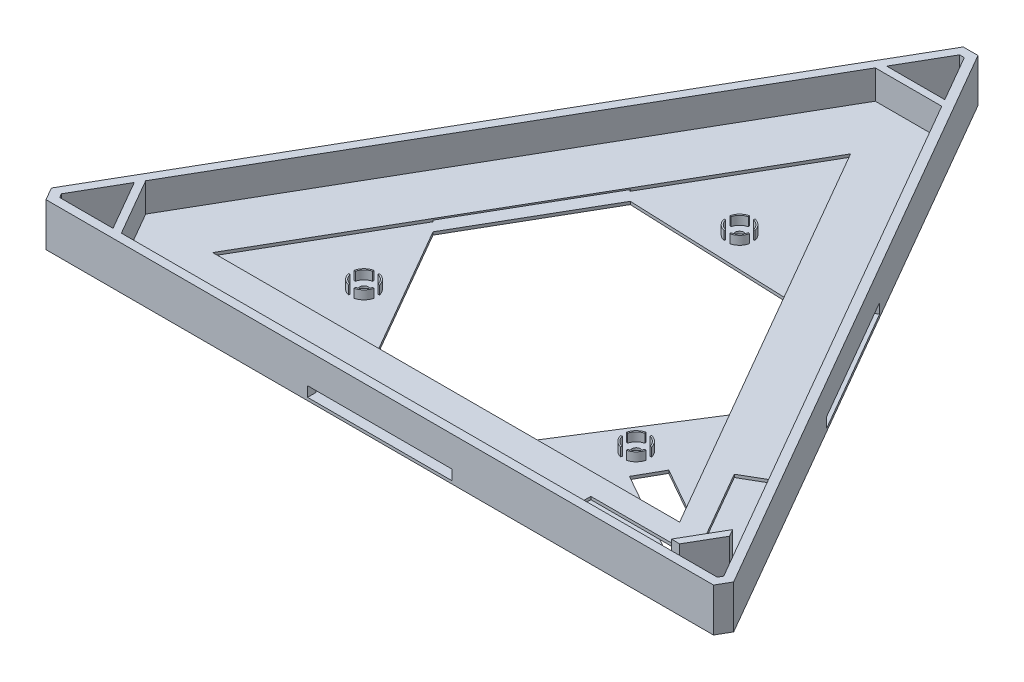
SolidWorks part; units mm, degrees
ref_plane "Front Plane" through (0, 0, 0) normal (0, 0, 1) x (1, 0, 0)
ref_plane "Top Plane" through (0, 0, 0) normal (0, 1, 0) x (1, 0, 0)
ref_plane "Right Plane" through (0, 0, 0) normal (1, 0, 0) x (0, 0, -1)
sketch "Sketch1" plane through (0, 0, 0) normal (0, 1, 0) x (1, 0, 0)
  line L0 (351.2729, 67.6655) -> (468.273, -134.9846)
  line L1 (347.2728, 67.6655) -> (347.2728, 65.1655) construction
  line L2 (409.773, -33.6595) -> (407.6079, -34.9095) construction
  line L3 (468.273, -134.9846) -> (464.2732, -141.9124)
  line L4 (230.2733, -141.9124) -> (464.2732, -141.9124)
  line L5 (230.2733, -141.9124) -> (226.2727, -134.9842)
  line L6 (226.2727, -134.9842) -> (343.2728, 67.6655)
  line L7 (353.4142, 63.9567) -> (351.2491, 62.7067) construction
  line L8 (347.2733, -141.9124) -> (347.2733, -139.4124) construction
  line L9 (231.7167, -139.4124) -> (462.8299, -139.4124)
  line L10 (284.7727, -33.6594) -> (286.9378, -34.9094) construction
  line L11 (344.7161, 65.1655) -> (349.8295, 65.1655)
  line L12 (465.3862, -134.9846) -> (349.8295, 65.1655)
  line L13 (466.2731, -138.4485) -> (464.1081, -137.1985) construction
  line L14 (462.8299, -139.4124) -> (465.3862, -134.9846)
  line L15 (229.1594, -134.9842) -> (344.7161, 65.1655)
  line L16 (229.1594, -134.9842) -> (231.7167, -139.4124)
  line L17 (286.9378, -34.9094) -> (287.3708, -35.1594) construction
  line L18 (230.438, -137.1983) -> (230.871, -136.9483) construction
  line L19 (232.0053, -138.9123) -> (229.7368, -134.9842)
  line L20 (343.2728, 67.6655) -> (351.2729, 67.6655)
  line L21 (345.0048, 64.6655) -> (229.7368, -134.9842)
  line L22 (349.5409, 64.6655) -> (345.0048, 64.6655)
  line L23 (249.0568, -126.4468) -> (246.8918, -127.697) construction
  line L24 (407.6079, -34.9095) -> (407.1749, -35.1595) construction
  line L26 (233.4463, -136.4089) -> (251.9226, -136.4093)
  line L27 (464.8089, -134.9846) -> (462.5412, -138.9123)
  line L28 (462.5412, -138.9123) -> (232.0053, -138.9123)
  line L29 (251.9226, -136.4093) -> (241.8609, -118.9847)
  line L30 (241.8609, -118.9847) -> (232.6236, -134.9842)
  line L31 (232.6236, -134.9842) -> (233.4463, -136.4089)
  line L33 (287.3708, -35.1594) -> (289.5359, -36.4094) construction
  line L34 (254.8093, -136.4089) -> (243.3042, -116.4848)
  line L35 (335.7675, 43.666) -> (243.3042, -116.4848)
  line L36 (358.7782, 43.666) -> (335.7675, 43.666)
  line L38 (289.5359, -36.4094) -> (306.8564, -46.4094) construction
  line L41 (461.939, -134.9846) -> (461.1164, -136.4093)
  line L42 (347.2688, -136.4172) -> (347.2688, -116.4172) construction
  line L43 (442.6021, -136.4093) -> (452.6999, -118.9847)
  line L44 (245.2636, -119.878) -> (249.0568, -126.4468) construction
  line L45 (452.6999, -118.9847) -> (461.939, -134.9846)
  line L48 (461.1164, -136.4093) -> (442.6021, -136.4093)
  line L49 (405.0134, -36.4027) -> (387.6936, -46.404) construction
  line L50 (306.8564, -46.4094) -> (466.2731, -138.4485) construction
  line L51 (357.3348, 46.166) -> (337.2109, 46.166)
  line L52 (337.2109, 46.166) -> (346.4484, 62.1659)
  line L53 (346.4484, 62.1659) -> (348.0966, 62.164)
  line L54 (348.0966, 62.164) -> (357.3348, 46.166)
  line L55 (228.273, -138.4483) -> (387.6936, -46.404) construction
  line L56 (347.2688, -116.4172) -> (347.2728, 43.666) construction
  line L57 (266.4391, -116.428) -> (428.1137, -116.4172)
  line L58 (347.2736, 23.6092) -> (428.1137, -116.4172)
  line L59 (266.4391, -116.428) -> (347.2736, 23.6092)
  line L60 (439.7283, -136.4254) -> (439.7283, -132.9254) construction
  line L61 (451.2487, -116.4715) -> (448.6507, -117.9717) construction
  line L62 (452.6999, -118.9847) -> (358.7782, 43.666)
  line L63 (442.6021, -136.4093) -> (254.8093, -136.4089)
  line L64 (441.749, -132.9254) -> (444.621, -132.9254)
  line L65 (448.6507, -117.9717) -> (450.9647, -121.979) construction
  line L66 (449.5167, -119.4714) -> (450.9647, -121.979)
  line L67 (441.749, -132.9254) -> (449.5167, -119.4714)
  line L68 (450.9647, -121.979) -> (444.621, -132.9254)
  line L69 (461.939, -134.9846) -> (427.2809, -114.9747) construction
  line L70 (461.1164, -136.4093) -> (426.4891, -116.4173) construction
  line L73 (405.0134, -134.9846) -> (439.7283, -134.9846)
  line L74 (405.0134, -134.9846) -> (405.0134, -124.0609)
  line L75 (405.0134, -124.0609) -> (439.7283, -124.0609)
  line L76 (439.7283, -134.9846) -> (439.7283, -124.0609)
  line L77 (405.0134, -124.0609) -> (430.3202, -80.2282) construction
  line L78 (405.0134, -134.9846) -> (433.4739, -85.6896) construction
  line L79 (461.1164, -136.4093) -> (424.3464, -72.7321) construction
  line L80 (432.6513, -87.1143) -> (423.1904, -92.5775)
  line L81 (432.6513, -87.1143) -> (450.1194, -117.365)
  line L82 (423.1904, -92.5775) -> (440.6585, -122.8281)
  line L83 (450.1194, -117.365) -> (440.6585, -122.8281)
  point P13 (407.6079, -34.9095)
  point P20 (464.1081, -137.1985)
  point P23 (347.2733, -139.4124)
  point P25 (347.2732, -141.9124)
  point P27 (347.2728, 65.1655)
  point P31 (286.9378, -34.9094)
  point P37 (287.3708, -35.1594)
  point P39 (230.871, -136.9483)
  point P41 (347.2728, 64.6655)
  point P45 (407.1749, -35.1595)
  point P50 (246.8918, -127.697)
  point P56 (289.5359, -36.4094)
  point P58 (249.0568, -126.4468)
  point P60 (347.2728, 43.666)
  point P62 (345.0048, -136.4089)
  point P64 (445.4885, -126.4485)
  point P71 (447.651, -127.697)
  point P77 (347.2728, 46.166)
  point P84 (347.2688, -116.4172)
  point P87 (387.6936, -46.404)
  point P89 (306.8564, -46.4094)
  point P100 (405.0134, -36.4027)
  dimension "D1" = 2.5
  dimension "D2" = 2.5
  dimension "D3" = 2.5
  dimension "D4" = 2.5
  dimension "D5" = 2.5
  dimension "D6" = 2.5
  dimension "D7" = 0.5
  dimension "D8" = 0.5
  dimension "D9" = 0.5
  dimension "D10" = 2.5
  dimension "D11" = 2.5
  dimension "D12" = 20
  dimension "D13" = 20
  dimension "D14" = 20
  dimension "D15" = 3.5
  dimension "D16" = 3
extrude "Boss-Extrude1" add sketch "Sketch1" along normal blind 1 contours L36 L35 L34 L57 L59 L58 region at (251.4484, 0, 125.0658)
extrude "Boss-Extrude2" add sketch "Sketch1<9>" along normal blind 11 contours L28 L27 L22 L21 L19 L31 L30 L29 L26 L34 L35 L36 L41 L48 L43 L45 L53 L54 L51 L52 | L68 L64 L67 L66 region at (230.7087, 0, 137.042)
sketch "Sketch1<9>" plane through (0, 0, 0) normal (0, 1, 0) x (1, 0, 0) same geometry as "Sketch1"
extrude "Boss-Extrude3" add sketch "Sketch1<10>" along normal blind 5 and the other way blind 3 contours L28 L27 L22 L21 L19 L31 L30 L29 L26 L34 L35 L36 L41 L48 L43 L45 L53 L54 L51 L52 | L68 L64 L67 L66 region at (230.7087, 0, 137.042)
sketch "Sketch1<10>" plane through (0, 0, 0) normal (0, 1, 0) x (1, 0, 0) same geometry as "Sketch1"
sketch "Sketch3" plane through (290.5896, 0, -167.772) normal (0.866, 0, -0.5) x (-0.5, 0, -0.866)
  line L1 (-261.593, -6.5) -> (-211.593, -6.5)
  line L2 (-261.593, -6.5) -> (-261.593, 0.5)
  line L3 (-261.593, 0.5) -> (-211.593, 0.5)
  line L4 (-211.593, -6.5) -> (-211.593, 0.5)
  line L5 (-261.593, -6.5) -> (-211.593, 0.5) construction
  line L6 (-261.593, 0.5) -> (-211.593, -6.5) construction
  point P0 (-236.593, -3)
  dimension "D1" = 50
  dimension "D2" = 7
extrude "Cut-Extrude3" cut sketch "Sketch3" against normal blind 25
sketch "Sketch5" plane through (0, 0, 139.4124) normal (0, 0, 1) x (1, 0, 0)
  line L0 (231.7167, -3) -> (462.8299, -3) construction
  line L1 (322.2733, -6.5) -> (372.2733, -6.5)
  line L2 (322.2733, -6.5) -> (322.2733, 0.5)
  line L3 (322.2733, 0.5) -> (372.2733, 0.5)
  line L4 (372.2733, -6.5) -> (372.2733, 0.5)
  line L5 (322.2733, -6.5) -> (372.2733, 0.5) construction
  line L6 (322.2733, 0.5) -> (372.2733, -6.5) construction
  point P0 (347.2733, -3)
  dimension "D1" = 50
  dimension "D2" = 7
extrude "Cut-Extrude4" cut sketch "Sketch5" against normal blind 25
sketch "Sketch6" plane through (230.3194, 0, 132.9752) normal (-0.866, 0, -0.5) x (-0.5, 0, 0.866)
  line L0 (2.3199, -3) -> (-228.7932, -3) construction
  line L1 (-138.2367, -6.5) -> (-88.2367, -6.5)
  line L2 (-138.2367, -6.5) -> (-138.2367, 0.5)
  line L3 (-138.2367, 0.5) -> (-88.2367, 0.5)
  line L4 (-88.2367, -6.5) -> (-88.2367, 0.5)
  line L5 (-138.2367, -6.5) -> (-88.2367, 0.5) construction
  line L6 (-138.2367, 0.5) -> (-88.2367, -6.5) construction
  point P0 (-113.2367, -3)
  dimension "D1" = 50
  dimension "D2" = 7
extrude "Cut-Extrude5" cut sketch "Sketch6" against normal blind 25
sketch "Sketch8" plane through (0, -3, 0) normal (0, -1, 0) x (1, 0, 0)
  line L1 (349.8295, -65.1655) -> (465.3862, 134.9846)
  line L2 (465.3862, 134.9846) -> (462.8299, 139.4124)
  line L6 (462.8299, 139.4124) -> (231.7167, 139.4124)
  line L7 (450.147, 123.2807) -> (452.6999, 118.9847)
  line L9 (452.6999, 118.9847) -> (461.939, 134.9846)
  line L12 (461.939, 134.9846) -> (461.1164, 136.4093)
  line L17 (461.1164, 136.4093) -> (442.6021, 136.4093)
  line L19 (322.2733, 116.4243) -> (294.3582, 68.0611)
  line L20 (294.3582, 68.0611) -> (319.3545, 24.7577)
  line L21 (319.3545, 24.7577) -> (376.4737, 26.9694)
  line L22 (376.4737, 26.9694) -> (401.4727, 70.2712)
  line L23 (401.4727, 70.2712) -> (372.2733, 116.4209)
  line L24 (372.2733, 116.4209) -> (322.2733, 116.4243)
  line L25 (386.873, 93.3461) -> (395.3235, 98.6928) construction
  line L30 (308.3157, 92.2427) -> (299.6549, 97.2417) construction
  line L31 (347.9141, 25.8635) -> (348.3013, 15.8635) construction
  line L34 (401.698, 107.3846) -> (445.2267, 131.9864)
  line L35 (450.147, 123.2807) -> (406.6183, 98.6788)
  line L36 (401.698, 107.3846) -> (406.6183, 98.6788)
  line L37 (231.7167, 139.4124) -> (229.1594, 134.9842)
  line L39 (233.4463, 136.4089) -> (251.9226, 136.4093)
  line L40 (251.9226, 136.4093) -> (241.8609, 118.9847)
  line L41 (241.8609, 118.9847) -> (232.6236, 134.9842)
  line L42 (232.6236, 134.9842) -> (233.4463, 136.4089)
  line L43 (349.8295, -65.1655) -> (344.7161, -65.1655)
  line L44 (344.7161, -65.1655) -> (229.1594, 134.9842)
  line L45 (337.2109, -46.166) -> (357.3348, -46.166)
  line L46 (357.3348, -46.166) -> (348.0966, -62.164)
  line L47 (348.0966, -62.164) -> (346.4484, -62.1659)
  line L48 (346.4484, -62.1659) -> (337.2109, -46.166)
  line L49 (442.6021, 136.4093) -> (445.2267, 131.9864)
  circle A0 centre (395.3235, 98.6928) radius 1.5
  circle A1 centre (348.3013, 15.8635) radius 1.5
  circle A2 centre (299.6549, 97.2417) radius 1.5
  dimension "D6" = 3
  dimension "D7" = 3
  dimension "D8" = 3
  dimension "D1" = 10
  dimension "D2" = 50
  dimension "D3" = 10
  dimension "D4" = 10
  dimension "D5" = 10
extrude "Boss-Extrude5" add sketch "Sketch8" along normal blind 1
sketch "Sketch12" plane through (0, -3, 0) normal (0, 1, 0) x (1, 0, 0)
  line L0 (348.3013, -11.8635) -> (348.3013, -11.3635) construction
  line L1 (348.3013, -11.3635) -> (349.2951, -11.4746) construction
  line L2 (349.2951, -11.4746) -> (349.1847, -11.9623)
  line L3 (348.3013, -11.3635) -> (347.3075, -11.4746) construction
  line L4 (347.3075, -11.4746) -> (347.4179, -11.9623)
  line L5 (352.3013, -15.8635) -> (352.8013, -15.8635) construction
  line L6 (344.3013, -15.8635) -> (343.8013, -15.8635) construction
  line L7 (348.3013, -19.8635) -> (348.3013, -20.3635) construction
  line L8 (352.8013, -15.8635) -> (352.6902, -14.8697) construction
  line L9 (352.8013, -15.8635) -> (352.6902, -16.8573) construction
  line L10 (343.8013, -15.8635) -> (343.9124, -14.8697) construction
  line L11 (343.8013, -15.8635) -> (343.9124, -16.8573) construction
  line L12 (348.3013, -20.3635) -> (349.2951, -20.2524) construction
  line L13 (348.3013, -20.3635) -> (347.3075, -20.2524) construction
  line L14 (343.9124, -14.8697) -> (348.3013, -15.8635) construction
  line L15 (348.3013, -15.8635) -> (352.6902, -14.8697) construction
  line L16 (343.9124, -16.8573) -> (348.3013, -15.8635) construction
  line L17 (348.3013, -15.8635) -> (352.6902, -16.8573) construction
  line L18 (347.3075, -20.2524) -> (348.3013, -15.8635) construction
  line L19 (348.3013, -15.8635) -> (349.2951, -20.2524) construction
  line L20 (343.9124, -14.8697) -> (344.4001, -14.9801)
  line L21 (343.9124, -16.8573) -> (344.4001, -16.7469)
  line L22 (347.3075, -20.2524) -> (347.4179, -19.7648)
  line L23 (349.2951, -20.2524) -> (349.1847, -19.7648)
  line L24 (352.6902, -14.8697) -> (352.2025, -14.9801)
  line L25 (352.6902, -16.8573) -> (352.2025, -16.7469)
  line L26 (395.3235, -94.1928) -> (395.3235, -98.6928) construction
  line L27 (395.3235, -98.6928) -> (390.8235, -98.6928) construction
  line L28 (390.8235, -98.6928) -> (390.9347, -97.699) construction
  line L29 (399.8235, -98.6928) -> (395.3235, -98.6928) construction
  line L30 (395.3235, -98.6928) -> (395.3235, -103.1928) construction
  line L31 (395.3235, -103.1928) -> (396.3173, -103.0817) construction
  line L32 (395.3235, -94.1928) -> (396.3173, -94.3039) construction
  line L33 (395.3235, -94.1928) -> (394.3297, -94.3039) construction
  line L34 (399.7124, -97.699) -> (399.8235, -98.6928) construction
  line L35 (399.8235, -98.6928) -> (399.7124, -99.6866) construction
  line L36 (390.9347, -99.6866) -> (390.8235, -98.6928) construction
  line L37 (394.3297, -103.0817) -> (395.3235, -103.1928) construction
  line L38 (394.3297, -94.3039) -> (395.3235, -98.6928) construction
  line L39 (395.3235, -98.6928) -> (396.3173, -94.3039) construction
  line L40 (390.9347, -99.6866) -> (395.3235, -98.6928) construction
  line L41 (395.3235, -98.6928) -> (390.9347, -97.699) construction
  line L42 (399.7124, -97.699) -> (395.3235, -98.6928) construction
  line L43 (395.3235, -98.6928) -> (399.7124, -99.6866) construction
  line L44 (394.3297, -103.0817) -> (395.3235, -98.6928) construction
  line L45 (395.3235, -98.6928) -> (396.3173, -103.0817) construction
  line L46 (394.3297, -94.3039) -> (394.4402, -94.7916)
  line L47 (396.3173, -94.3039) -> (396.2069, -94.7916)
  line L48 (399.7124, -97.699) -> (399.2248, -97.8094)
  line L49 (399.7124, -99.6866) -> (399.2248, -99.5762)
  line L50 (396.3173, -103.0817) -> (396.2069, -102.5941)
  line L51 (394.3297, -103.0817) -> (394.4402, -102.5941)
  line L52 (390.9347, -99.6866) -> (391.4223, -99.5762)
  line L53 (390.9347, -97.699) -> (391.4248, -97.7985)
  line L54 (299.6549, -92.7417) -> (299.6549, -97.2417) construction
  line L55 (299.6549, -97.2417) -> (304.1549, -97.2417) construction
  line L56 (299.6549, -101.7417) -> (299.6549, -97.2417) construction
  line L57 (299.6549, -97.2417) -> (295.1549, -97.2417) construction
  line L58 (299.6549, -97.2417) -> (298.6611, -92.8528) construction
  line L59 (298.6611, -92.8528) -> (299.6549, -92.7417) construction
  line L60 (299.6549, -92.7417) -> (300.6487, -92.8528) construction
  line L61 (300.6487, -92.8528) -> (299.6549, -97.2417) construction
  line L62 (299.6549, -97.2417) -> (304.0438, -96.2479) construction
  line L63 (304.0438, -96.2479) -> (304.1549, -97.2417) construction
  line L64 (304.1549, -97.2417) -> (304.0438, -98.2355) construction
  line L65 (304.0438, -98.2355) -> (299.6549, -97.2417) construction
  line L66 (299.6549, -97.2417) -> (300.6487, -101.6306) construction
  line L67 (300.6487, -101.6306) -> (299.6549, -101.7417) construction
  line L68 (299.6549, -101.7417) -> (298.6611, -101.6306) construction
  line L69 (298.6611, -101.6306) -> (299.6549, -97.2417) construction
  line L70 (299.6549, -97.2417) -> (295.266, -98.2355) construction
  line L71 (295.266, -98.2355) -> (295.1549, -97.2417) construction
  line L72 (295.1549, -97.2417) -> (295.266, -96.2479) construction
  line L73 (295.266, -96.2479) -> (299.6549, -97.2417) construction
  line L74 (295.266, -96.2479) -> (295.7537, -96.3583)
  line L75 (295.266, -98.2355) -> (295.7537, -98.1251)
  line L76 (298.6611, -101.6306) -> (298.7715, -101.1429)
  line L77 (300.6487, -101.6306) -> (300.5383, -101.1429)
  line L78 (304.0438, -98.2355) -> (303.5561, -98.1251)
  line L79 (304.0438, -96.2479) -> (303.5561, -96.3583)
  line L80 (300.6487, -92.8528) -> (300.5383, -93.3404)
  line L81 (298.6611, -92.8528) -> (298.7715, -93.3404)
  circle A0 centre (348.3013, -15.8635) radius 4.5
  circle A1 centre (395.3235, -98.6928) radius 4.5
  circle A2 centre (299.6549, -97.2417) radius 4.5
  circle A3 centre (348.3013, -15.8635) radius 4
  circle A4 centre (395.3235, -98.6928) radius 4
  circle A5 centre (299.6549, -97.2417) radius 4
  dimension "D1" = 9
  dimension "D2" = 9
  dimension "D3" = 9
  dimension "D4" = 8
  dimension "D5" = 8
  dimension "D6" = 8
  dimension "D7" = 1
  dimension "D8" = 1
  dimension "D9" = 1
  dimension "D10" = 1
  dimension "D11" = 1
  dimension "D12" = 1
  dimension "D13" = 1
  dimension "D14" = 1
  dimension "D15" = 1
  dimension "D16" = 1
  dimension "D17" = 1
  dimension "D18" = 1
  dimension "D19" = 1
  dimension "D20" = 1
  dimension "D21" = 1
  dimension "D22" = 1
  dimension "D23" = 1
  dimension "D24" = 1
  dimension "D25" = 1
  dimension "D26" = 1
  dimension "D27" = 1
  dimension "D28" = 1
  dimension "D29" = 1
  dimension "D30" = 1
extrude "Boss-Extrude10" add sketch "Sketch12" along normal blind 3 contours A3 L4 A0 L20 | A3 L24 A0 L2 | A3 L23 A0 L25 | A3 L21 A0 L22 | A4 L46 A1 L53 | A4 L48 A1 L47 | A4 L50 A1 L49 | A4 L52 A1 L51 | A5 L81 A2 L74 | A5 L79 A2 L80 | A5 L77 A2 L78 | A5 L75 A2 L76 region at (351.1537, -3, 13.0111) region at (345.4489, -3, 13.0111) region at (351.1537, -3, 18.7159) region at (345.4489, -3, 18.7159) region at (392.4726, -3, 95.8382) region at (398.1759, -3, 95.8404) region at (392.4712, -3, 101.5452) region at (398.1759, -3, 101.5452) region at (296.8025, -3, 94.3893) region at (296.8025, -3, 100.0941) region at (302.5073, -3, 94.3893) region at (302.5073, -3, 100.0941)
